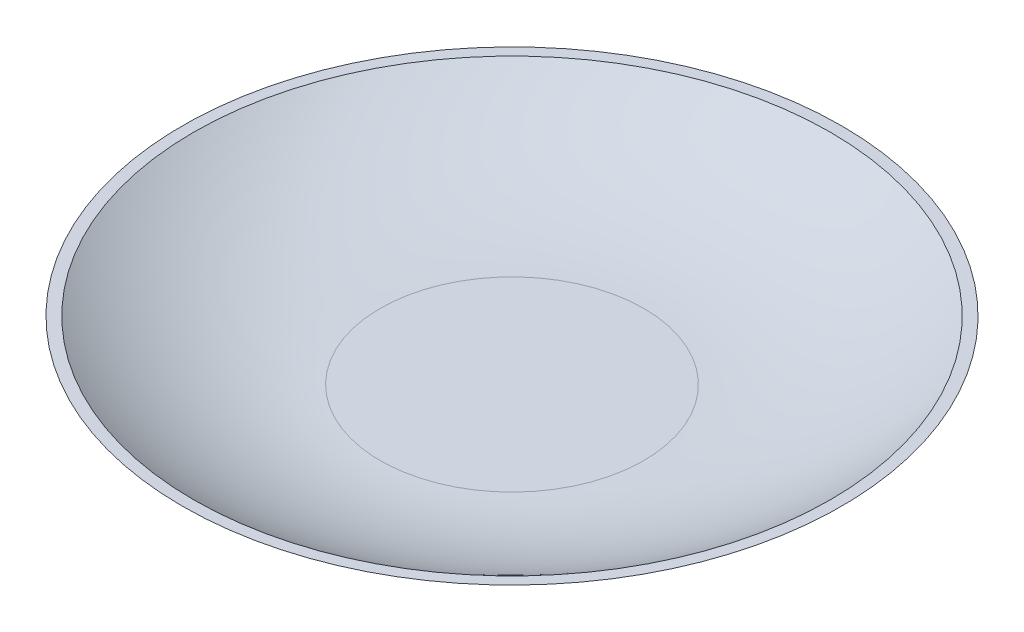
SolidWorks part; units mm, degrees
material "Titanium Ti-8Al-1Mo-1V"
ref_plane "Front Plane" through (0, 0, 0) normal (0, 0, 1) x (1, 0, 0)
ref_plane "Top Plane" through (0, 0, 0) normal (0, 1, 0) x (1, 0, 0)
ref_plane "Right Plane" through (0, 0, 0) normal (1, 0, 0) x (0, 0, -1)
sketch "Sketch1" plane through (0, 0, 0) normal (0, 1, 0) x (1, 0, 0)
  circle A0 centre (0, 0) radius 2500
  dimension "D1" = 5000
extrude "Boss-Extrude1" add sketch "Sketch1" against normal blind 500 contours A0
fillet "Fillet1" radius 2500 1 edges at (0, -500, 2500)
shell "Shell1" thickness 50 removed face at (0, 0, 2500)
